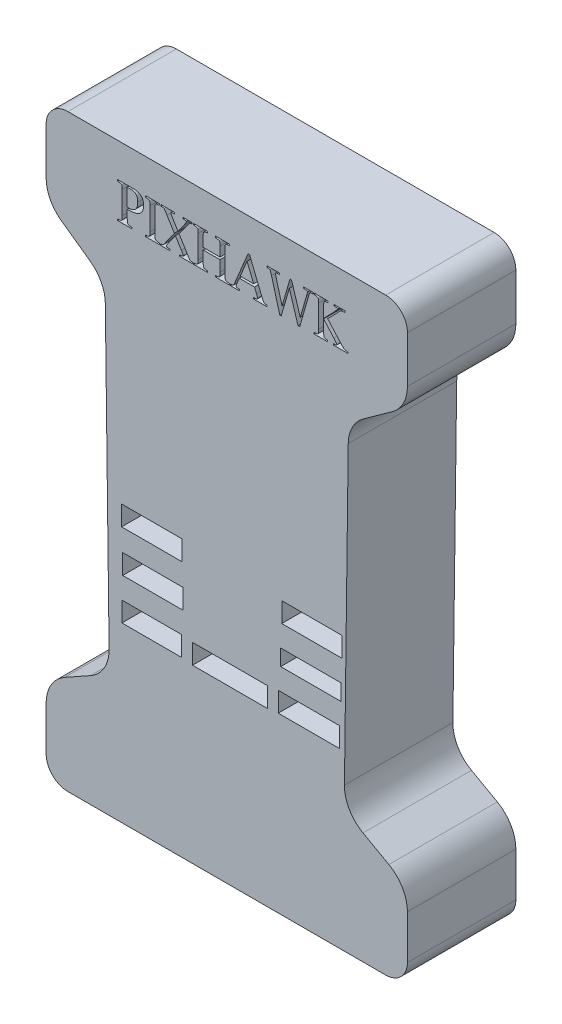
SolidWorks part; units mm, degrees
ref_plane "Front Plane" through (0, 0, 0) normal (0, 0, 1) x (1, 0, 0)
ref_plane "Top Plane" through (0, 0, 0) normal (0, 1, 0) x (1, 0, 0)
ref_plane "Right Plane" through (0, 0, 0) normal (1, 0, 0) x (0, 0, -1)
sketch "Sketch1" plane through (0, 0, 0) normal (0, 0, 1) x (1, 0, 0)
  line L0 (21.935, 39.7402) -> (-21.935, 39.7402)
  line L1 (0, 99.4803) -> (0, -108.8309) construction
  line L2 (-24.935, 36.7402) -> (-24.935, 30.3132)
  line L3 (-22.8412, 26.2446) -> (-18.8589, 23.4001)
  line L4 (-16.7655, 19.3949) -> (-16.2434, -21.6954)
  line L5 (-18.8039, -26.1236) -> (-22.3741, -28.1188)
  line L6 (-24.935, -32.4835) -> (-24.935, -38.5498)
  line L7 (-21.935, -41.5498) -> (21.935, -41.5498)
  line L8 (24.935, -32.4835) -> (24.935, -38.5498)
  line L9 (18.8039, -26.1236) -> (22.3741, -28.1188)
  line L10 (24.935, 36.7402) -> (24.935, 30.3132)
  line L11 (16.7655, 19.3949) -> (16.2434, -21.6954)
  line L12 (22.8412, 26.2446) -> (18.8589, 23.4001)
  arc A0 (-16.7655, 19.3949) -> (-18.8589, 23.4001) centre (-21.7651, 19.3314) ccw
  arc A1 (-24.935, 30.3132) -> (-22.8412, 26.2446) centre (-19.935, 30.3132) ccw
  arc A2 (-21.935, 39.7402) -> (-24.935, 36.7402) centre (-21.935, 36.7402) ccw
  arc A3 (-16.2434, -21.6954) -> (-18.8039, -26.1236) centre (-21.243, -21.7589) cw
  arc A4 (-22.3741, -28.1188) -> (-24.935, -32.4835) centre (-19.935, -32.4835) ccw
  arc A5 (-21.935, -41.5498) -> (-24.935, -38.5498) centre (-21.935, -38.5498) cw
  arc A6 (21.935, -41.5498) -> (24.935, -38.5498) centre (21.935, -38.5498) ccw
  arc A7 (22.3741, -28.1188) -> (24.935, -32.4835) centre (19.935, -32.4835) cw
  arc A8 (21.935, 39.7402) -> (24.935, 36.7402) centre (21.935, 36.7402) cw
  arc A9 (24.935, 30.3132) -> (22.8412, 26.2446) centre (19.935, 30.3132) cw
  arc A10 (16.2434, -21.6954) -> (18.8039, -26.1236) centre (21.243, -21.7589) ccw
  arc A11 (16.7655, 19.3949) -> (18.8589, 23.4001) centre (21.7651, 19.3314) cw
  point P40 (0, -41.5498)
  point P41 (0, 39.7402)
  dimension "D1" = 5
  dimension "D2" = 5
  dimension "D3" = 3
  dimension "D4" = 5
  dimension "D5" = 5
  dimension "D6" = 3
  dimension "D7" = 0.728
  dimension "D8" = 24.935
  dimension "D9" = 24.935
  dimension "D10" = 81.29
extrude "Boss-Extrude1" add sketch "Sketch1" along normal blind 14.97
sketch "Sketch2" plane through (-16.5164, -0.2099, 0) normal (-0.9999, -0.0127, 0) x (0, 0, 1)
  line L0 (0, 19.6064) -> (0, -21.4873) construction
  line L1 (5, -18.0917) -> (9.97, -18.0917)
  line L2 (5, -18.0917) -> (5, -2.0917)
  line L3 (5, -2.0917) -> (9.97, -2.0917)
  line L4 (9.97, -18.0917) -> (9.97, -2.0917)
  line L5 (14.97, 19.6064) -> (14.97, -21.4873) construction
  dimension "D1" = 5
  dimension "D2" = 5
  dimension "D3" = 16
extrude "Cut-Extrude1" cut sketch "Sketch2" against normal blind 10
sketch "Sketch4" plane through (0, 0, 14.97) normal (0, 0, 1) x (1, 0, 0)
  line L0 (-6.017, -11.9298) -> (-14.3672, -11.9298)
  line L1 (-6.2296, -17.6639) -> (-14.4781, -17.6639)
  line L2 (-6.2296, -17.6639) -> (-6.2296, -14.9298)
  line L3 (-6.2296, -14.9298) -> (-14.4781, -14.9298)
  line L4 (-14.4781, -17.6639) -> (-14.4781, -14.9298)
  line L5 (-6.017, -11.9298) -> (-6.017, -9.1956)
  line L6 (-6.017, -9.1956) -> (-14.3672, -9.1956)
  line L7 (-14.3672, -11.9298) -> (-14.3672, -9.1956)
  line L8 (15.558, -17.6594) -> (7.106, -17.6594)
  line L9 (15.558, -17.6594) -> (15.558, -14.9252)
  line L10 (15.558, -14.9252) -> (7.106, -14.9252)
  line L11 (7.106, -17.6594) -> (7.106, -14.9252)
  line L12 (15.7912, -11.9252) -> (7.4409, -11.9252)
  line L13 (15.7912, -11.9252) -> (15.7912, -9.7001)
  line L14 (15.7912, -9.7001) -> (7.4409, -9.7001)
  line L15 (7.4409, -11.9252) -> (7.4409, -9.7001)
  line L16 (-6.1648, -6.1956) -> (-14.515, -6.1956)
  line L17 (-6.1648, -6.1956) -> (-6.1648, -3.4615)
  line L18 (-6.1648, -3.4615) -> (-14.515, -3.4615)
  line L19 (-14.515, -6.1956) -> (-14.515, -3.4615)
  line L20 (15.939, -6.7001) -> (7.5887, -6.7001)
  line L21 (15.939, -6.7001) -> (15.939, -3.966)
  line L22 (15.939, -3.966) -> (7.5887, -3.966)
  line L23 (7.5887, -6.7001) -> (7.5887, -3.966)
  line L24 (5.606, -17.8449) -> (-4.7296, -17.8449)
  line L25 (5.606, -17.8449) -> (5.606, -15.1108)
  line L26 (5.606, -15.1108) -> (-4.7296, -15.1108)
  line L27 (-4.7296, -17.8449) -> (-4.7296, -15.1108)
  point P31 (-10.1921, -11.9298)
  dimension "D1" = 3
  dimension "D2" = 3
  dimension "D3" = 1.5
  dimension "D4" = 1.5
  dimension "D5" = 3
  dimension "D6" = 3
extrude "Cut-Extrude3" cut sketch "Sketch4" against normal blind 3
sketch "Sketch5" plane through (0, 0, 14.97) normal (0, 0, 1) x (1, 0, 0)
  text T0 "PIXHAWK" font "Lucida Bright" height in points 18
extrude "Cut-Extrude4" cut sketch "Sketch5" against normal blind 3
scale "Scale3" scale about centroid uniform scaling yes scale factor 1.9
scale "Scale6" scale about centroid uniform scaling yes scale factor 0.7
